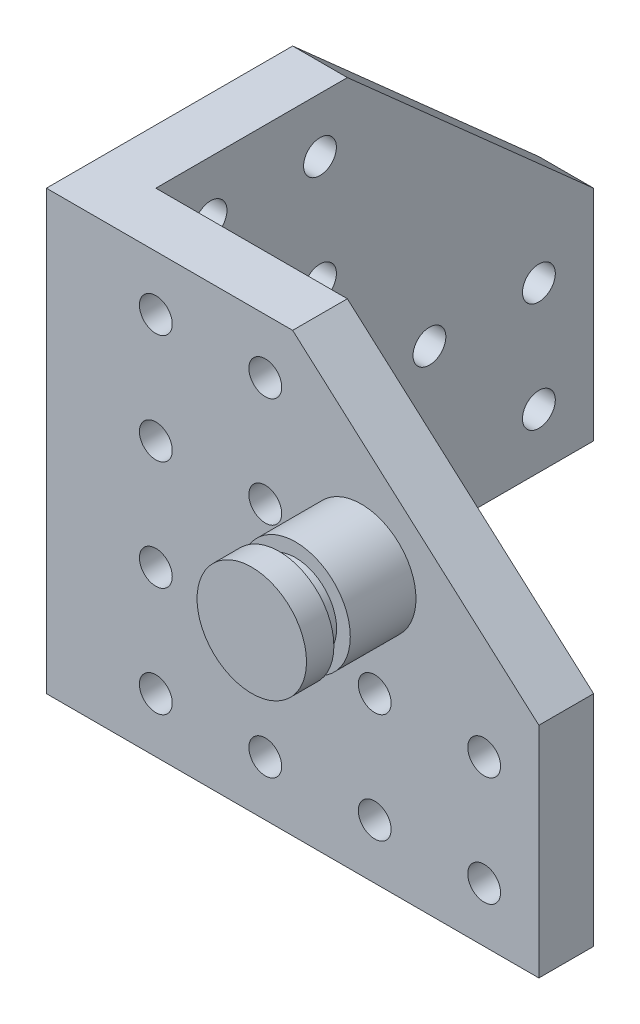
SolidWorks part; units mm, degrees
ref_plane "Front Plane" through (0, 0, 0) normal (0, 0, 1) x (1, 0, 0)
ref_plane "Top Plane" through (0, 0, 0) normal (0, 1, 0) x (1, 0, 0)
ref_plane "Right Plane" through (0, 0, 0) normal (1, 0, 0) x (0, 0, -1)
sketch "Sketch1" plane through (0, 0, 0) normal (0, 1, 0) x (1, 0, 0)
  line L0 (0, 0) -> (90, 0)
  line L1 (90, 0) -> (90, 10)
  line L2 (90, 10) -> (10, 10)
  line L3 (10, 10) -> (10, 90)
  line L4 (10, 90) -> (0, 90)
  line L5 (0, 90) -> (0, 0)
  dimension "D1" = 90
  dimension "D2" = 90
  dimension "D3" = 10
  dimension "D4" = 10
extrude "Boss-Extrude1" add sketch "Sketch1" along normal blind 80
sketch "Sketch2" plane through (0, 0, 0) normal (0, 0, 1) x (1, 0, 0)
  line L0 (45, 80) -> (90, 40)
  line L1 (0, 80) -> (90, 80) construction
  line L2 (90, 80) -> (90, 0) construction
  line L3 (90, 40) -> (90, 80)
  line L4 (90, 80) -> (45, 80)
extrude "Cut-Extrude1" cut sketch "Sketch2" against normal up to next
sketch "Sketch3" plane through (0, 0, 0) normal (-1, 0, 0) x (0, 0, 1)
  line L0 (-45, 80) -> (-90, 40)
  line L1 (-90, 80) -> (0, 80) construction
  line L2 (-90, 80) -> (-90, 0) construction
  line L3 (-90, 40) -> (-90, 80)
  line L4 (-90, 80) -> (-45, 80)
extrude "Cut-Extrude2" cut sketch "Sketch3" against normal up to next
sketch "Sketch4" plane through (0, 0, 0) normal (0, 0, 1) x (1, 0, 0)
  line L0 (0, 0) -> (90, 0) construction
  line L1 (0, 80) -> (45, 80) construction
  line L2 (0, 80) -> (0, 0) construction
  line L3 (90, 40) -> (90, 0) construction
  circle A0 centre (20, 70) radius 3
  circle A1 centre (40, 70) radius 3
  circle A2 centre (40, 50) radius 3
  circle A3 centre (20, 30) radius 3
  circle A4 centre (40, 10) radius 3
  circle A5 centre (20, 50) radius 3
  circle A6 centre (40, 30) radius 3
  circle A7 centre (20, 10) radius 3
  circle A8 centre (60, 30) radius 3
  circle A9 centre (80, 10) radius 3
  circle A10 centre (80, 30) radius 3
  circle A11 centre (60, 10) radius 3
  point P16 (9.8261, 17.6732)
  point P25 (0, 0)
  point P26 (0, 0)
  point P27 (0, 0)
  point P28 (0, 0)
  point P29 (0, 0)
  point P30 (0, 0)
  point P31 (0, 0)
  point P32 (0, 0)
  point P33 (0, 0)
  point P42 (40, 70)
  point P43 (0, 0)
  dimension "D1" = 6
  dimension "D2" = 10
  dimension "D3" = 20
  dimension "D4" = 10
  dimension "D5" = 20
  dimension "D6" = 20
  dimension "D7" = 20
  dimension "D8" = 20
  dimension "D9" = 10
extrude "Cut-Extrude3" cut sketch "Sketch4" against normal up to next
sketch "Sketch5" plane through (0, 0, 0) normal (-1, 0, 0) x (0, 0, 1)
  line L0 (-45, 80) -> (0, 80) construction
  line L1 (-90, 0) -> (0, 0) construction
  line L2 (0, 80) -> (0, 0) construction
  line L3 (-90, 40) -> (-90, 0) construction
  circle A0 centre (-20, 30) radius 2.5
  circle A1 centre (-40, 30) radius 2.5
  circle A2 centre (-40, 10) radius 2.5
  circle A3 centre (-20, 10) radius 2.5
  circle A5 centre (-20, 70) radius 3
  circle A6 centre (-40, 70) radius 3
  circle A7 centre (-40, 50) radius 3
  circle A8 centre (-20, 50) radius 3
  circle A9 centre (-60, 30) radius 3
  circle A10 centre (-80, 30) radius 3
  circle A11 centre (-80, 10) radius 3
  circle A12 centre (-60, 10) radius 3
  point P24 (0, 0)
  point P25 (0, 0)
  point P26 (0, 0)
  point P27 (0, 0)
  point P28 (0, 0)
  point P29 (0, 0)
  point P30 (0, 0)
  point P31 (0, 0)
  point P32 (0, 0)
  dimension "D1" = 5
  dimension "D2" = 6
  dimension "D3" = 10
  dimension "D4" = 20
  dimension "D5" = 20
  dimension "D6" = 10
  dimension "D7" = 20
  dimension "D8" = 20
  dimension "D9" = 20
  dimension "D10" = 10
extrude "Cut-Extrude4" cut sketch "Sketch5" against normal up to next
sketch "Sketch6" plane through (0, 0, 0) normal (-1, 0, 0) x (0, 0, 1)
  line L0 (-67.5, 60) -> (-47.5691, 37.5777) construction
  line L1 (-90, 40) -> (-45, 80) construction
  circle A0 centre (-57.5345, 48.7889) radius 10
  point P6 (0, 0)
  dimension "D2" = 20
  dimension "D1" = 90
  dimension "D3" = 15
extrude "Boss-Extrude2" add sketch "Sketch6" along normal blind 20
sketch "Sketch7" plane through (-20, 0, 0) normal (-1, 0, 0) x (0, 0, 1)
  circle A0 centre (-57.5345, 48.7889) radius 10
  circle A1 centre (-57.5345, 48.7889) radius 7.5
  dimension "D1" = 15
  dimension "D2" = 20
extrude "Cut-Extrude5" cut sketch "Sketch7" against normal blind 3 from offset 5 offset against normal yes
sketch "Sketch8" plane through (0, 0, 0) normal (0, 0, 1) x (1, 0, 0)
  line L0 (67.5, 60) -> (47.5691, 37.5777) construction
  line L1 (45, 80) -> (90, 40) construction
  circle A0 centre (57.5345, 48.7889) radius 10
  point P6 (0, 0)
  dimension "D3" = 20
  dimension "D1" = 90
  dimension "D2" = 15
extrude "Boss-Extrude3" add sketch "Sketch8" along normal blind 20
sketch "Sketch9" plane through (0, 0, 20) normal (0, 0, 1) x (1, 0, 0)
  circle A0 centre (57.5345, 48.7889) radius 10
  circle A1 centre (57.5345, 48.7889) radius 7.5
  dimension "D1" = 20
  dimension "D2" = 15
extrude "Cut-Extrude6" cut sketch "Sketch9" against normal blind 3 from offset 5 offset against normal yes
